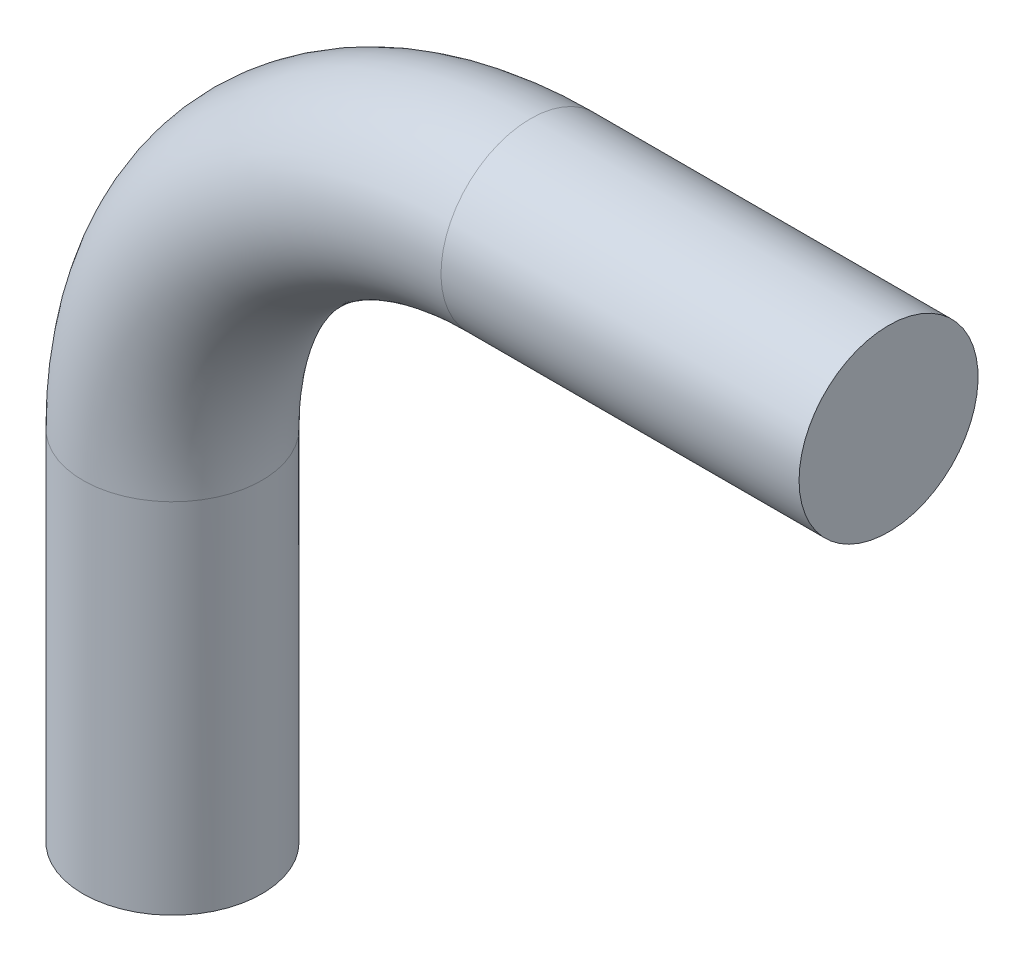
SolidWorks part; units mm, degrees
ref_plane "Front Plane" through (0, 0, 0) normal (0, 0, 1) x (1, 0, 0)
ref_plane "Top Plane" through (0, 0, 0) normal (0, 1, 0) x (1, 0, 0)
ref_plane "Right Plane" through (0, 0, 0) normal (1, 0, 0) x (0, 0, -1)
sketch "Sketch1" plane through (0, 0, 0) normal (0, 1, 0) x (1, 0, 0)
  circle A0 centre (0, 0) radius 25
  dimension "D1" = 50
sketch "Sketch2" plane through (0, 0, 0) normal (0, 0, 1) x (1, 0, 0)
  line L0 (0, 0) -> (0, 100)
  line L1 (100, 200) -> (200, 200)
  arc A0 (100, 200) -> (0, 100) centre (100, 100) ccw
  dimension "D2" = 100
  dimension "D1" = 100
  dimension "D3" = 100
sweep "Sweep1" add profiles "Sketch1" path "Sketch2"
ref_axis "Axis1" through (100, 200, 0) along (1, 0, 0)
ref_plane "Plane1" through (0, 0, 0) normal (0, 0, 1) x (1, 0, 0)
ref_plane "Plane2" through (0, 200, 0) normal (0, -1, 0) x (1, 0, 0)
ref_axis "Axis2" through (100, 100, 0) along (0, 0, 1)
ref_point "Point1"
ref_plane "Plane3" through (100, 100, 0) normal (0.7071, 0.7071, 0) x (0, 0, 1)
